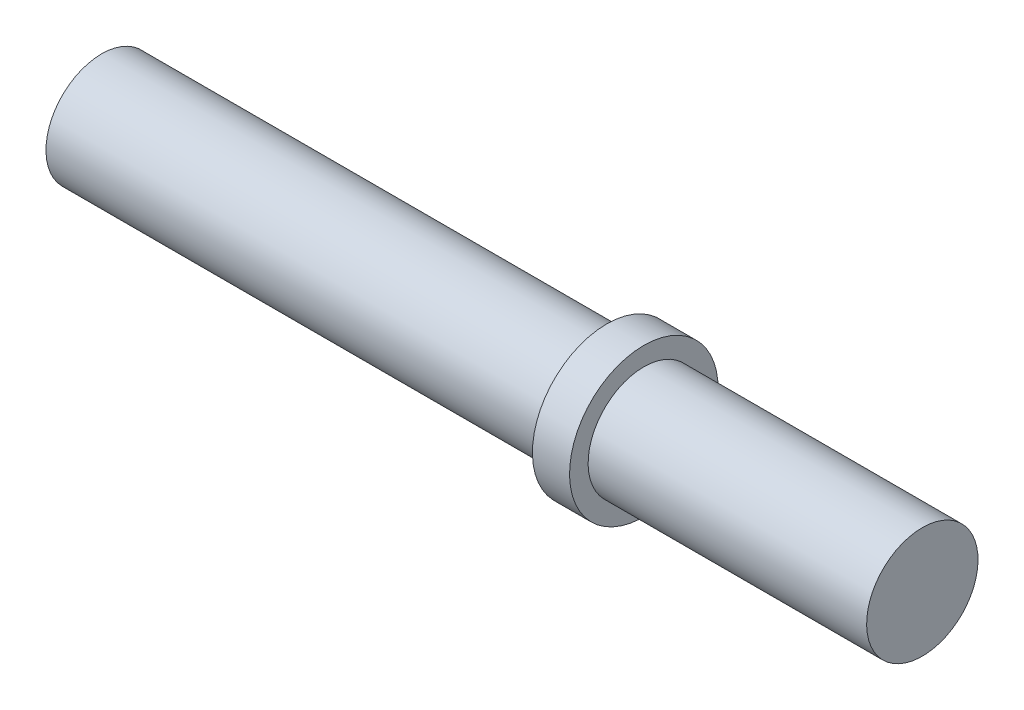
SolidWorks part; units mm, degrees
ref_plane "Front Plane" through (0, 0, 0) normal (0, 0, 1) x (1, 0, 0)
ref_plane "Top Plane" through (0, 0, 0) normal (0, 1, 0) x (1, 0, 0)
ref_plane "Right Plane" through (0, 0, 0) normal (1, 0, 0) x (0, 0, -1)
sketch "Sketch1" plane through (0, 0, 0) normal (0, 0, 1) x (1, 0, 0)
  line L0 (0, 3) -> (0, 0)
  line L1 (0, 0) -> (27.2, 0)
  line L2 (27.2, 0) -> (27.2, -1)
  line L3 (27.2, -1) -> (29.2, -1)
  line L4 (29.2, -1) -> (29.2, 0)
  line L5 (29.2, 0) -> (44.2, 0)
  line L6 (44.2, 0) -> (44.2, 3)
  line L7 (44.2, 3) -> (0, 3)
  point P2 (12.455, 0.8734)
  point P10 (0, 0)
  point P12 (0, 0)
  point P13 (0, 0)
  dimension "D1" = 44.2
  dimension "D2" = 27.2
  dimension "D3" = 2
  dimension "D4" = 3
  dimension "D5" = 1
revolve "Revolve1" add sketch "Sketch1" angle 360 about L7
